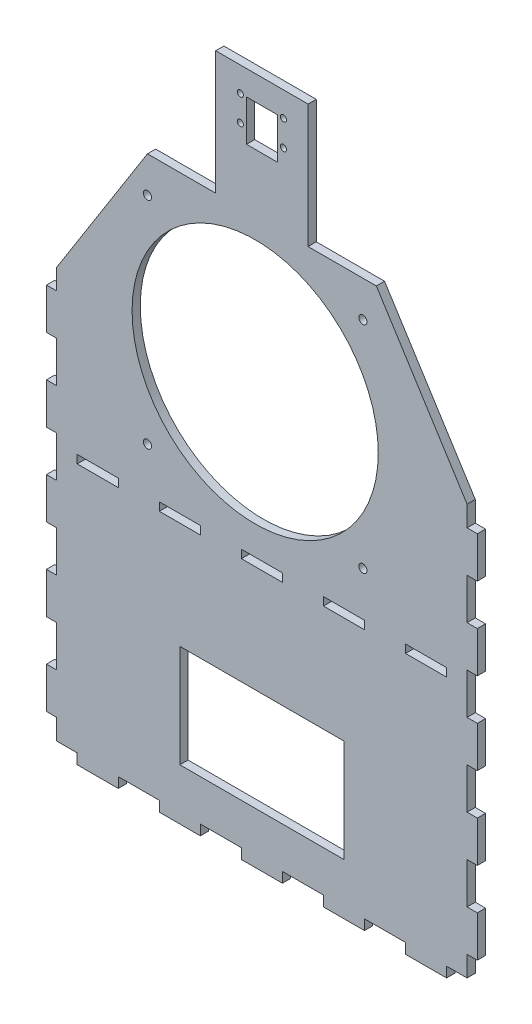
SolidWorks part; units mm, degrees
ref_plane "Přední rovina" through (0, 0, 0) normal (0, 0, 1) x (1, 0, 0)
ref_plane "Horní rovina" through (0, 0, 0) normal (0, 1, 0) x (1, 0, 0)
ref_plane "Pravá rovina" through (0, 0, 0) normal (1, 0, 0) x (0, 0, -1)
sketch "Skica1" plane through (0, 0, 0) normal (0, 0, 1) x (1, 0, 0)
  line L0 (-21.5981, -113.24) -> (-21.5981, -95.4761)
  line L1 (-121.5981, -113.24) -> (78.4019, -113.24)
  line L2 (-121.5981, -113.24) -> (-121.5981, 156.76)
  line L3 (-121.5981, 156.76) -> (78.4019, 156.76)
  line L4 (78.4019, -113.24) -> (78.4019, 156.76)
  line L5 (-111.5981, -113.24) -> (-91.5981, -113.24)
  line L6 (-111.5981, -113.24) -> (-111.5981, -118.24)
  line L7 (-111.5981, -118.24) -> (-91.5981, -118.24)
  line L8 (-91.5981, -113.24) -> (-91.5981, -118.24)
  line L9 (-71.5981, -113.24) -> (-51.5981, -113.24)
  line L10 (-71.5981, -113.24) -> (-71.5981, -118.24)
  line L11 (-71.5981, -118.24) -> (-51.5981, -118.24)
  line L12 (-51.5981, -113.24) -> (-51.5981, -118.24)
  line L13 (-31.5981, -113.24) -> (-11.5981, -113.24)
  line L14 (-31.5981, -113.24) -> (-31.5981, -118.24)
  line L15 (-31.5981, -118.24) -> (-11.5981, -118.24)
  line L16 (-11.5981, -113.24) -> (-11.5981, -118.24)
  line L17 (28.4019, -118.24) -> (8.4019, -118.24)
  line L18 (8.4019, -113.24) -> (8.4019, -118.24)
  line L19 (28.4019, -113.24) -> (8.4019, -113.24)
  line L20 (28.4019, -113.24) -> (28.4019, -118.24)
  line L21 (68.4019, -118.24) -> (48.4019, -118.24)
  line L22 (48.4019, -113.24) -> (48.4019, -118.24)
  line L23 (68.4019, -113.24) -> (48.4019, -113.24)
  line L24 (68.4019, -113.24) -> (68.4019, -118.24)
  line L25 (78.4019, 36.76) -> (83.4019, 36.76)
  line L26 (-121.5981, -103.24) -> (-126.5981, -103.24)
  line L27 (-121.5981, -103.24) -> (-121.5981, -83.24)
  line L28 (-121.5981, -83.24) -> (-126.5981, -83.24)
  line L29 (-126.5981, -103.24) -> (-126.5981, -83.24)
  line L30 (-121.5981, -63.24) -> (-126.5981, -63.24)
  line L31 (-121.5981, -63.24) -> (-121.5981, -43.24)
  line L32 (-121.5981, -43.24) -> (-126.5981, -43.24)
  line L33 (-126.5981, -63.24) -> (-126.5981, -43.24)
  line L34 (-121.5981, -23.24) -> (-126.5981, -23.24)
  line L35 (-121.5981, -23.24) -> (-121.5981, -3.24)
  line L36 (-121.5981, -3.24) -> (-126.5981, -3.24)
  line L37 (-126.5981, -23.24) -> (-126.5981, -3.24)
  line L38 (-121.5981, 16.76) -> (-126.5981, 16.76)
  line L39 (-121.5981, 16.76) -> (-121.5981, 36.76)
  line L40 (-121.5981, 36.76) -> (-126.5981, 36.76)
  line L41 (-126.5981, 16.76) -> (-126.5981, 36.76)
  line L42 (83.4019, 16.76) -> (83.4019, 36.76)
  line L43 (78.4019, 16.76) -> (83.4019, 16.76)
  line L44 (78.4019, 16.76) -> (78.4019, 36.76)
  line L45 (78.4019, -3.24) -> (83.4019, -3.24)
  line L46 (83.4019, -23.24) -> (83.4019, -3.24)
  line L47 (78.4019, -23.24) -> (83.4019, -23.24)
  line L48 (78.4019, -23.24) -> (78.4019, -3.24)
  line L49 (78.4019, -43.24) -> (83.4019, -43.24)
  line L50 (83.4019, -63.24) -> (83.4019, -43.24)
  line L51 (78.4019, -63.24) -> (83.4019, -63.24)
  line L52 (78.4019, -63.24) -> (78.4019, -43.24)
  line L53 (78.4019, -83.24) -> (83.4019, -83.24)
  line L54 (83.4019, -103.24) -> (83.4019, -83.24)
  line L55 (78.4019, -103.24) -> (83.4019, -103.24)
  line L56 (78.4019, -103.24) -> (78.4019, -83.24)
  line L57 (-77.3799, 156.76) -> (-121.5981, 86.76)
  line L58 (-111.5981, 12.76) -> (-91.5981, 12.76)
  line L59 (-111.5981, 12.76) -> (-111.5981, 8.76)
  line L60 (-111.5981, 8.76) -> (-91.5981, 8.76)
  line L61 (-91.5981, 12.76) -> (-91.5981, 8.76)
  line L62 (-71.5981, 12.76) -> (-51.5981, 12.76)
  line L63 (-71.5981, 12.76) -> (-71.5981, 8.76)
  line L64 (-71.5981, 8.76) -> (-51.5981, 8.76)
  line L65 (-51.5981, 12.76) -> (-51.5981, 8.76)
  line L66 (-31.5981, 12.76) -> (-11.5981, 12.76)
  line L67 (-31.5981, 12.76) -> (-31.5981, 8.76)
  line L68 (-31.5981, 8.76) -> (-11.5981, 8.76)
  line L69 (-11.5981, 12.76) -> (-11.5981, 8.76)
  line L70 (8.4019, 12.76) -> (28.4019, 12.76)
  line L71 (8.4019, 12.76) -> (8.4019, 8.76)
  line L72 (8.4019, 8.76) -> (28.4019, 8.76)
  line L73 (28.4019, 12.76) -> (28.4019, 8.76)
  line L74 (48.4019, 12.76) -> (68.4019, 12.76)
  line L75 (48.4019, 12.76) -> (48.4019, 8.76)
  line L76 (48.4019, 8.76) -> (68.4019, 8.76)
  line L77 (68.4019, 12.76) -> (68.4019, 8.76)
  line L78 (-121.5981, 56.76) -> (-126.5981, 56.76)
  line L79 (-121.5981, 56.76) -> (-121.5981, 76.76)
  line L80 (-121.5981, 76.76) -> (-126.5981, 76.76)
  line L81 (-126.5981, 56.76) -> (-126.5981, 76.76)
  line L82 (34.1836, 156.76) -> (78.4019, 86.76)
  line L83 (78.4019, 76.76) -> (83.4019, 76.76)
  line L84 (83.4019, 56.76) -> (83.4019, 76.76)
  line L85 (78.4019, 56.76) -> (83.4019, 56.76)
  line L86 (78.4019, 56.76) -> (78.4019, 76.76)
  line L88 (-44.0981, 156.76) -> (0.9019, 156.76)
  line L89 (-44.0981, 156.76) -> (-44.0981, 216.8991)
  line L90 (-44.0981, 216.8991) -> (0.9019, 216.8991)
  line L91 (0.9019, 156.76) -> (0.9019, 216.8991)
  line L92 (-29.0981, 204.8991) -> (-14.0981, 204.8991)
  line L93 (-29.0981, 204.8991) -> (-29.0981, 184.8991)
  line L94 (-29.0981, 184.8991) -> (-14.0981, 184.8991)
  line L95 (-14.0981, 204.8991) -> (-14.0981, 184.8991)
  line L96 (-61.5981, -93.24) -> (18.4019, -93.24)
  line L97 (-61.5981, -93.24) -> (-61.5981, -43.24)
  line L98 (-61.5981, -43.24) -> (18.4019, -43.24)
  line L99 (18.4019, -93.24) -> (18.4019, -43.24)
  circle A0 centre (-24.8799, 86.76) radius 60
  circle A1 centre (-77.3799, 139.26) radius 2
  circle A2 centre (27.6201, 139.26) radius 2
  circle A3 centre (27.6201, 34.26) radius 2
  circle A4 centre (-77.3799, 34.26) radius 2
  circle A5 centre (-32.0981, 204.8991) radius 1.5
  circle A6 centre (-11.0981, 204.8991) radius 1.5
  circle A7 centre (-11.0981, 192.3991) radius 1.5
  circle A8 centre (-32.0981, 192.3991) radius 1.5
  point P89 (-121.5981, 86.76)
  point P93 (-77.3799, 156.76)
  dimension "D3" = 120
  dimension "D4" = 70
  dimension "D6" = 4
  dimension "D7" = 4
  dimension "D8" = 4
  dimension "D9" = 4
  dimension "D35" = 3
  dimension "D36" = 3
  dimension "D37" = 3
  dimension "D38" = 3
  dimension "D1" = 270
  dimension "D2" = 200
  dimension "D5" = 105
  dimension "D10" = 105
  dimension "D11" = 52.5
  dimension "D12" = 52.5
  dimension "D13" = 20
  dimension "D14" = 20
  dimension "D15" = 20
  dimension "D16" = 20
  dimension "D17" = 10
  dimension "D18" = 20
  dimension "D19" = 5
  dimension "D20" = 10
  dimension "D21" = 20
  dimension "D22" = 20
  dimension "D23" = 20
  dimension "D24" = 20
  dimension "D25" = 20
  dimension "D26" = 20
  dimension "D27" = 20
  dimension "D28" = 5
  dimension "D29" = 4
  dimension "D30" = 20
  dimension "D31" = 20
  dimension "D32" = 10
  dimension "D33" = 4
  dimension "D34" = 45
  dimension "D39" = 12.5
  dimension "D40" = 21
  dimension "D41" = 12
  dimension "D42" = 12
  dimension "D43" = 12
  dimension "D44" = 15
  dimension "D45" = 3
  dimension "D46" = 20
  dimension "D47" = 22.5
  dimension "D48" = 50
  dimension "D49" = 80
  dimension "D50" = 20
  dimension "D51" = 40
  dimension "D52" = 10
extrude "Přidat vysunutím1" add sketch "Skica1" along normal blind 4 contours L8 L1 L6 L7 | L41 L38 L2 L40 | L37 L34 L2 L36 | L1 L4 L3 L2 A4 A3 A2 A1 A0 L58 L61 L60 L59 L62 L65 | L42 L25 L44 L43 | L46 L45 L48 L47 | L50 L49 L52 L51 | L54 L53 L56 L55 | L21 L22 L23 L24 | L17 L18 L19 L20 | L15 L16 L13 L14 | L11 L12 L9 L10 | L29 L28 L27 L26 | L33 L32 L31 L30 | L79 L78 L81 L80 | L83 L84 L85 L86 | L89 L88 L91 L90 | L93 L92 L95 L94 | A7 | A8 | A5 | A6 region at (-20.5374, 1.2835, 0) region at (-101.5981, -115.74, 0) region at (-124.0981, -13.24, 0) region at (-124.0981, 26.76, 0)
